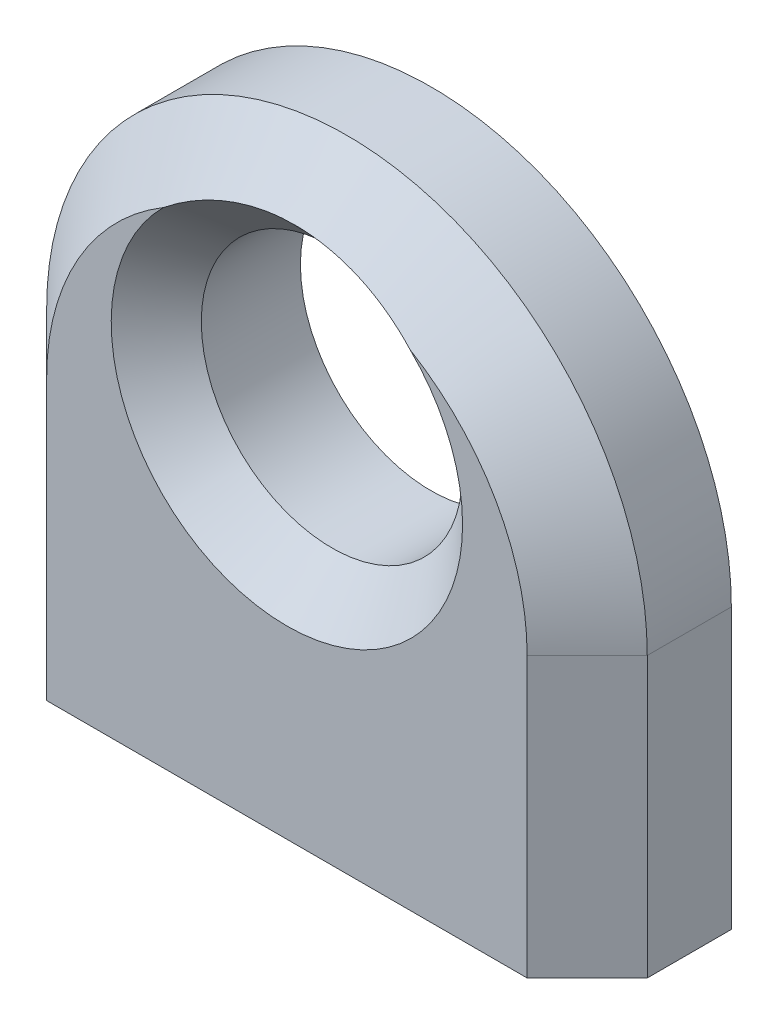
SolidWorks part; units mm, degrees
ref_plane "Front Plane" through (0, 0, 0) normal (0, 0, 1) x (1, 0, 0)
ref_plane "Top Plane" through (0, 0, 0) normal (0, 1, 0) x (1, 0, 0)
ref_plane "Right Plane" through (0, 0, 0) normal (1, 0, 0) x (0, 0, -1)
sketch "Sketch1" plane through (0, 0, 0) normal (0, 0, 1) x (1, 0, 0)
  line L0 (5, 0) -> (5, 4.9) construction
  line L5 (0, 0) -> (10, 0)
  line L6 (0, 0) -> (0, 4.6507)
  line L8 (10, 0) -> (10, 4.6507)
  arc A1 (0, 4.6507) -> (10, 4.6507) centre (5, 4.6507) cw
  point P0 (0, 0)
  dimension "D1" = 10
  dimension "D2" = 4.9
extrude "Boss-Extrude1" add sketch "Sketch1" along normal blind 2.4
ref_plane "Plane1" through (0, 0, 2.4) normal (0, 0, 1) x (1, 0, 0)
sketch "Sketch2" plane through (0, 0, 2.4) normal (0, 0, 1) x (1, 0, 0)
  line L0 (5, 0) -> (5, 6) construction
  line L1 (0, 0) -> (10, 0) construction
  circle A0 centre (5, 6) radius 2.175
  dimension "D1" = 6
  dimension "D2" = 4.35
extrude "Cut-Extrude1" cut sketch "Sketch2" against normal blind 3
chamfer "Chamfer1" distance 1 angle 45 3 edges at (10, 2.3254, 2.4) (5, 9.6507, 2.4) (0, 2.3254, 2.4)
chamfer "Chamfer2" distance 0.75 angle 45 1 edges at (7.175, 6, 2.4)
sketch "Sketch3" plane through (0, 0, 0) normal (0, 0, -1) x (-1, 0, 0)
  line L0 (-9.8189, 0.1902) -> (-0.2719, 0.1902) construction
  text T0 "out"
extrude "Cut-Extrude2" cut sketch "Sketch3" against normal blind 0.4
